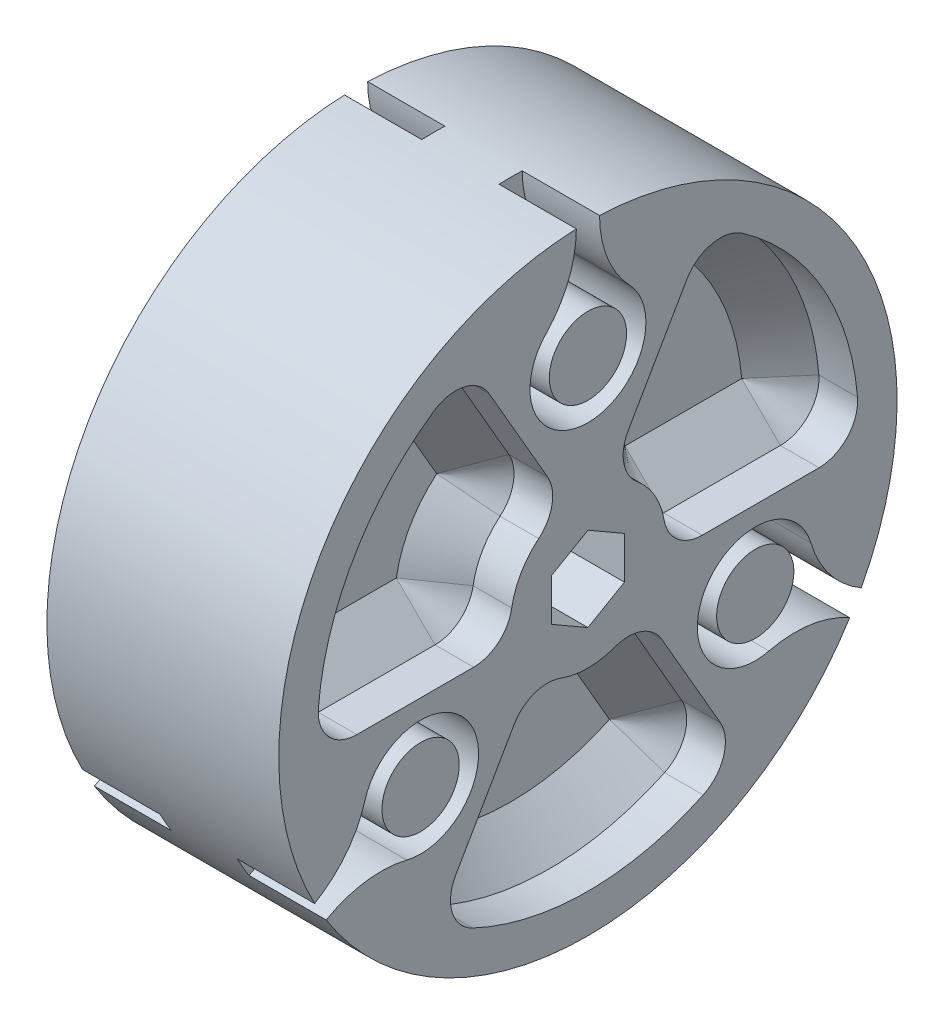
SolidWorks part; units mm, degrees
note: '?' marks a value the reader was unsure of.
ref_plane "Front Plane" through (0, 0, 0) normal (0, 0, 1) x (1, 0, 0)
ref_plane "Top Plane" through (0, 0, 0) normal (0, 1, 0) x (1, 0, 0)
ref_plane "Right Plane" through (0, 0, 0) normal (1, 0, 0) x (0, 0, -1)
sketch "Sketch1" plane through (0, 0, 0) normal (1, 0, 0) x (0, 0, -1)
  circle A0 centre (0, 0) radius 25.4
  dimension "D1" = 50.8
extrude "Boss-Extrude2" add sketch "Sketch1" along normal mid plane 6.35
sketch "Sketch3" plane through (0, 0, 0) normal (1, 0, 0) x (0, 0, -1)
  circle A0 centre (0, 0) radius 6.35
  dimension "D1" = 12.7
extrude "Boss-Extrude3" add sketch "Sketch3" against normal mid plane 19.05
ref_axis "Axis1" through (0, 0, 0) along (1, 0, 0)?
sketch "Sketch5" plane through (9.525, 0, 0) normal (1, 0, 0) x (0, 0, -1)
  line L0 (-0.9525, 25.3821) -> (-0.9525, 34.0271) construction
  line L2 (0, 0) -> (0, 25.4) construction
  line L3 (-1.6994, 6.1184) -> (-9.7093, 19.992)
  line L5 (1.6994, 6.1184) -> (9.7093, 19.992)
  line L7 (0, 0) -> (23.8682, 8.6873) construction
  line L8 (20.8847, 7.6014) -> (23.8682, 8.6873)
  line L9 (9.7093, 19.992) -> (11.3004, 22.7478) construction
  line L10 (-20.8847, 7.6014) -> (-23.8682, 8.6873)
  line L11 (-9.7093, 19.992) -> (-11.3004, 22.7478) construction
  line L12 (-1.6994, 6.1184) -> (1.6994, 6.1184)
  circle A0 centre (0, 0) radius 25.4 construction
  arc A1 (-9.7093, 19.992) -> (-20.8847, 7.6014) centre (0, 0) ccw
  circle A2 centre (0, 15.875) radius 3.175
  circle A3 centre (0, 15.875) radius 4.7625 construction
  arc A4 (-3.4444, 19.1639) -> (3.4444, 19.1639) centre (0, 15.875) ccw
  arc A5 (-3.4444, 19.1639) -> (-0.9525, 25.3821) centre (-9.9566, 25.3821) ccw
  arc A6 (0.9525, 25.3821) -> (3.4444, 19.1639) centre (9.9566, 25.3821) ccw
  arc A7 (11.3004, 22.7478) -> (-11.3004, 22.7478) centre (0, 0) ccw
  arc A8 (-11.3004, 22.7478) -> (-23.8682, 8.6873) centre (0, 0) ccw
  arc A11 (11.3004, 22.7478) -> (23.8682, 8.6873) centre (0, 0) cw
  arc A12 (9.7093, 19.992) -> (20.8847, 7.6014) centre (0, 0) cw
  circle A13 centre (0, 0) radius 6.35 construction
  circle A14 centre (0, 0) radius 6.35 construction
  dimension "D1" = 6.35
  dimension "D4" = 9.525
  dimension "D7" = 1.5875
  dimension "D2" = 9.525
  dimension "D3" = 1.905
  dimension "D5" = 60
  dimension "D9" = 3.175
  dimension "D10" = 70
extrude "Boss-Extrude4" add sketch "Sketch5" against normal up to surface (19.05 mm away)
pattern_circular "CirPattern5" count 3 over 360 about axis through (0, 0, 0) along (1, 0, 0) of "Boss-Extrude4"
fillet "Fillet1" radius 3.175 12 edges at (6.35, -1.5875, 22.1682) (6.35, -1.5875, 6.1484) (6.35, -4.5309, 4.449) (6.35, -18.4045, 12.4589) (6.35, -18.4045, -12.4589) (6.35, -4.5309, -4.449) (6.35, -1.5875, -6.1484) (6.35, -1.5875, -22.1682) (6.35, 19.992, -9.7093) (6.35, 6.1184, -1.6994) (6.35, 6.1184, 1.6994) (6.35, 19.992, 9.7093)
fillet "Fillet2" radius 3.175 12 edges at (-6.35, -18.4045, 12.4589) (-6.35, -1.5875, 22.1682) (-6.35, -1.5875, 6.1484) (-6.35, -4.5309, 4.449) (-6.35, -18.4045, -12.4589) (-6.35, -4.5309, -4.449) (-6.35, -1.5875, -6.1484) (-6.35, -1.5875, -22.1682) (-6.35, 19.992, 9.7093) (-6.35, 19.992, -9.7093) (-6.35, 6.1184, -1.6994) (-6.35, 6.1184, 1.6994)
sketch "Sketch6" plane through (9.525, 0, 0) normal (1, 0, 0) x (0, 0, -1)
  line L1 (0, 3.4641) -> (-3, 1.7321)
  line L2 (-3, 1.7321) -> (-3, -1.7321)
  line L3 (-3, -1.7321) -> (0, -3.4641)
  line L4 (0, -3.4641) -> (3, -1.7321)
  line L5 (3, -1.7321) -> (3, 1.7321)
  line L6 (3, 1.7321) -> (0, 3.4641)
  circle A0 centre (0, 0) radius 3 construction
  point P1 (0, 0)
  dimension "D1" = 6
extrude "Cut-Extrude2" cut sketch "Sketch6" against normal through all both and the other way through all
chamfer "Chamfer1" distance 3.175 angle 45 48 edges at (3.175, 3.175, 5.4993) (3.175, -1.5875, 14.1878) (3.175, 13.0807, 5.7191) (3.175, 11.1125, 19.2474) (3.175, -0.562, 21.3205) (3.175, 18.7451, 10.1735) (3.175, 6.7774, 2.9459) (3.175, -0.8374, 7.3423) (3.175, -1.5875, -14.1878) (3.175, 3.175, -5.4993) (3.175, 11.1125, -19.2474) (3.175, 13.0807, -5.7191) (3.175, 18.7451, -10.1735) (3.175, -0.562, -21.3205) (3.175, 6.7774, -2.9459) (3.175, -0.8374, -7.3423) (3.175, -6.35, 0) (3.175, -11.4932, -8.4687) (3.175, -11.4932, 8.4687) (3.175, -22.225, 0) (3.175, -18.1831, -11.1469) (3.175, -18.1831, 11.1469) (3.175, -5.9399, 4.3964) (3.175, -5.9399, -4.3964) (-3.175, -1.5875, -14.1878) (-3.175, 3.175, -5.4993) (-3.175, 13.0807, -5.7191) (-3.175, 11.1125, -19.2474) (-3.175, 18.7451, -10.1735) (-3.175, -0.562, -21.3205) (-3.175, 6.7774, -2.9459) (-3.175, -0.8374, -7.3423) (-3.175, -11.4932, 8.4687) (-3.175, -6.35, 0) (-3.175, -11.4932, -8.4687) (-3.175, -22.225, 0) (-3.175, -18.1831, 11.1469) (-3.175, -18.1831, -11.1469) (-3.175, -5.9399, -4.3964) (-3.175, -5.9399, 4.3964) (-3.175, 13.0807, 5.7191) (-3.175, 3.175, 5.4993) (-3.175, -1.5875, 14.1878) (-3.175, 11.1125, 19.2474) (-3.175, 18.7451, 10.1735) (-3.175, -0.562, 21.3205) (-3.175, -0.8374, 7.3423) (-3.175, 6.7774, 2.9459)
